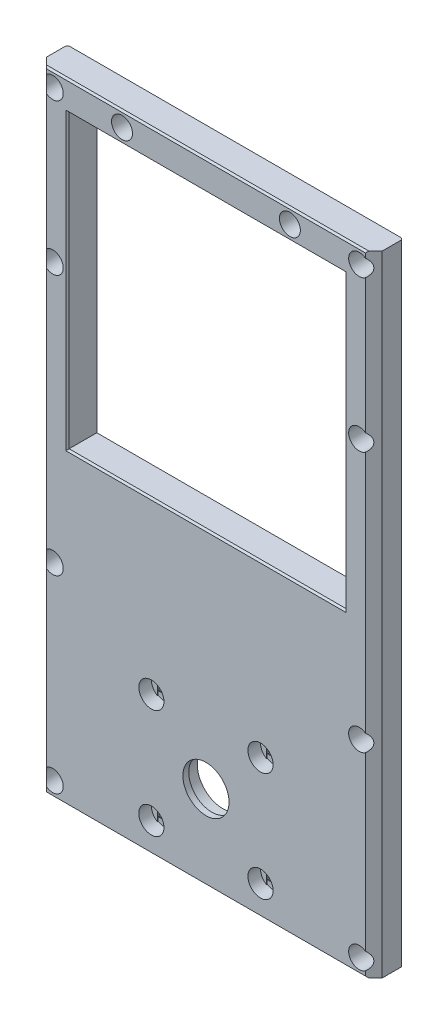
SolidWorks part; units mm, degrees
ref_plane "Front Plane" through (0, 0, 0) normal (0, 0, 1) x (1, 0, 0)
ref_plane "Top Plane" through (0, 0, 0) normal (0, 1, 0) x (1, 0, 0)
ref_plane "Right Plane" through (0, 0, 0) normal (1, 0, 0) x (0, 0, -1)
sketch "Sketch1" plane through (0, 0, 0) normal (0, 0, 1) x (1, 0, 0)
  line L1 (-40, -75) -> (40, -75)
  line L2 (-40, -75) -> (-40, 75)
  line L3 (-40, 75) -> (40, 75)
  line L4 (40, -75) -> (40, 75)
  line L5 (-40, -75) -> (40, 75) construction
  line L6 (-40, 75) -> (40, -75) construction
  line L7 (-33, -68) -> (33, -68)
  line L8 (-33, -68) -> (-33, 68)
  line L9 (-33, 68) -> (33, 68)
  line L10 (33, -68) -> (33, 68)
  line L11 (-33, -68) -> (33, 68) construction
  line L12 (-33, 68) -> (33, -68) construction
  point P0 (0, 0)
  point P6 (0, 0)
  dimension "D1" = 150
  dimension "D2" = 80
  dimension "D3" = 7
  dimension "D4" = 7
extrude "Boss-Extrude1" add sketch "Sketch1" along normal blind 7
sketch "Sketch2" plane through (0, 0, 7) normal (0, 0, 1) x (1, 0, 0)
  line L0 (33, -68) -> (33, 68) construction
  line L1 (-33, -68) -> (33, -68)
  line L2 (-33, -68) -> (-33, -32)
  line L3 (-33, -32) -> (33, -32)
  line L4 (33, -68) -> (33, -32)
  dimension "D1" = 36
extrude "Boss-Extrude2" add sketch "Sketch2" against normal up to surface (7 mm away) up to face at (0, 0, 0)
sketch "Sketch3" plane through (0, 0, 0) normal (0, 0, -1) x (-1, 0, 0)
  line L0 (0, -75) -> (0, -55) construction
  line L1 (40, -75) -> (-40, -75) construction
  circle A0 centre (0, -55) radius 5.5
  dimension "D1" = 11
  dimension "D2" = 20
extrude "Cut-Extrude1" cut sketch "Sketch3" against normal through all
sketch "Sketch4" plane through (0, 0, 0) normal (0, 0, -1) x (-1, 0, 0)
  circle A0 centre (0, -55) radius 6.05
  dimension "D1" = 12.1
extrude "Cut-Extrude2" cut sketch "Sketch4" against normal offset from surface (5.6 mm away) 1.4 up to face at (-5.5, -55, 7)
sketch "Sketch5" plane through (0, 0, 0) normal (0, 0, -1) x (-1, 0, 0)
  circle A0 centre (0, -55) radius 11.1
  dimension "D1" = 22.2
extrude "Cut-Extrude3" cut sketch "Sketch5" against normal offset from surface (3 mm away) 2.6 up to face at (-6.05, -55, 5.6)
sketch "Sketch6" plane through (0, 0, 0) normal (0, 0, -1) x (-1, 0, 0)
  line L1 (-13, -68) -> (13, -68) construction
  line L2 (-13, -68) -> (-13, -42) construction
  line L3 (-13, -42) -> (13, -42) construction
  line L4 (13, -68) -> (13, -42) construction
  line L5 (-13, -68) -> (13, -42) construction
  line L6 (-13, -42) -> (13, -68) construction
  circle A0 centre (-13, -42) radius 1.6
  circle A1 centre (13, -42) radius 1.6
  circle A2 centre (13, -68) radius 1.6
  circle A3 centre (-13, -68) radius 1.6
  point P0 (0, -55)
  dimension "D2" = 3.2
  dimension "D1" = 26
extrude "Cut-Extrude4" cut sketch "Sketch6" against normal through all
sketch "Sketch7" plane through (0, 0, 0) normal (0, 0, -1) x (-1, 0, 0)
  line L1 (-25, -74) -> (25, -74)
  line L2 (-25, -74) -> (-25, -36)
  line L3 (-25, -36) -> (25, -36)
  line L4 (25, -74) -> (25, -36)
  line L5 (-25, -74) -> (25, -36) construction
  line L6 (-25, -36) -> (25, -74) construction
  point P0 (0, -55)
  dimension "D1" = 50
  dimension "D2" = 38
extrude "Cut-Extrude5" cut sketch "Sketch7" against normal blind 1
sketch "Sketch8" plane through (0, 0, 7) normal (0, 0, 1) x (1, 0, 0)
  circle A0 centre (-13, -42) radius 3
  circle A1 centre (13, -42) radius 3
  circle A2 centre (13, -68) radius 3
  circle A3 centre (-13, -68) radius 3
  dimension "D1" = 6
extrude "Cut-Extrude6" cut sketch "Sketch8" against normal blind 3
sketch "Sketch9" plane through (0, 0, 7) normal (0, 0, 1) x (1, 0, 0)
  line L0 (-40, 75) -> (-40, -75) construction
  line L1 (-36.5, -71.5) -> (36.5, -71.5) construction
  line L2 (-36.5, -71.5) -> (-36.5, 71.5) construction
  line L3 (-36.5, 71.5) -> (36.5, 71.5) construction
  line L4 (36.5, -71.5) -> (36.5, 71.5) construction
  line L5 (-36.5, -71.5) -> (36.5, 71.5) construction
  line L6 (-36.5, 71.5) -> (36.5, -71.5) construction
  line L7 (40, 75) -> (-40, 75) construction
  circle A0 centre (-36.5, 71.5) radius 1.35
  circle A1 centre (36.5, 71.5) radius 1.35
  circle A2 centre (36.5, -71.5) radius 1.35
  circle A3 centre (-36.5, -71.5) radius 1.35
  circle A6 centre (-36.5, 35.5) radius 1.35
  circle A7 centre (-36.5, -26.5) radius 1.35
  circle A8 centre (36.5, -26.5) radius 1.35
  circle A9 centre (36.5, 35.5) radius 1.35
  point P0 (0, 0)
  dimension "D3" = 2.7
  dimension "D4" = 45
  dimension "D5" = 36
  dimension "D1" = 3.5
  dimension "D2" = 3.5
extrude "Cut-Extrude7" cut sketch "Sketch9" against normal through all
sketch "Sketch10" plane through (0, 0, 7) normal (0, 0, 1) x (1, 0, 0)
  circle A0 centre (-36.5, 71.5) radius 2.5
  circle A1 centre (36.5, 71.5) radius 2.5
  circle A2 centre (-36.5, 35.5) radius 2.5
  circle A3 centre (-36.5, -26.5) radius 2.5
  circle A4 centre (-36.5, -71.5) radius 2.5
  circle A5 centre (36.5, -71.5) radius 2.5
  circle A6 centre (36.5, 35.5) radius 2.5
  circle A7 centre (36.5, -26.5) radius 2.5
  dimension "D1" = 5
extrude "Cut-Extrude8" cut sketch "Sketch10" against normal blind 5
chamfer "Chamfer1" distance 2 angle 45 2 edges at (-40, 0, 7) (40, 0, 7)
sketch "Sketch11" plane through (0, 0, 7) normal (0, 0, 1) x (1, 0, 0)
  line L0 (33, -32) -> (33, 68) construction
  line L1 (-33, -32) -> (33, -32)
  line L2 (-33, -32) -> (-33, -1.5)
  line L3 (-33, -1.5) -> (33, -1.5)
  line L4 (33, -32) -> (33, -1.5)
  line L5 (-38, -75) -> (38, -75) construction
  dimension "D1" = 73.5
extrude "Boss-Extrude3" add sketch "Sketch11" against normal up to surface (7 mm away) up to face at (37.85, 71.5, 0)
sketch "Sketch12" plane through (0, 0, 2) normal (0, 0, 1) x (1, 0, 0)
  line L2 (-37.85, -73.6042) -> (-37.85, -69.3958)
  line L4 (-35.15, -73.6042) -> (-35.15, -69.3958)
  line L5 (-37.85, -73.6042) -> (-35.15, -69.3958) construction
  line L6 (-37.85, -69.3958) -> (-35.15, -73.6042) construction
  line L8 (-37.85, -28.6042) -> (-37.85, -24.3958)
  line L10 (-35.15, -28.6042) -> (-35.15, -24.3958)
  line L11 (-37.85, -28.6042) -> (-35.15, -24.3958) construction
  line L12 (-37.85, -24.3958) -> (-35.15, -28.6042) construction
  line L14 (-37.85, 33.3958) -> (-37.85, 37.6042)
  line L16 (-35.15, 33.3958) -> (-35.15, 37.6042)
  line L17 (-37.85, 33.3958) -> (-35.15, 37.6042) construction
  line L18 (-37.85, 37.6042) -> (-35.15, 33.3958) construction
  line L20 (-37.85, 69.3958) -> (-37.85, 73.6042)
  line L22 (-35.15, 69.3958) -> (-35.15, 73.6042)
  line L23 (-37.85, 69.3958) -> (-35.15, 73.6042) construction
  line L24 (-37.85, 73.6042) -> (-35.15, 69.3958) construction
  arc A0 (-38, -73.5) -> (-38, -69.5) centre (-36.5, -71.5) ccw construction
  circle A1 centre (-36.5, -26.5) radius 2.5 construction
  circle A2 centre (-36.5, 35.5) radius 2.5 construction
  arc A3 (-38, 69.5) -> (-38, 73.5) centre (-36.5, 71.5) ccw construction
  circle A4 centre (-36.5, 71.5) radius 1.35 construction
  circle A5 centre (-36.5, 71.5) radius 2.5 construction
  arc A6 (-35.15, 73.6042) -> (-37.85, 73.6042) centre (-36.5, 71.5) ccw
  arc A7 (-37.85, 69.3958) -> (-35.15, 69.3958) centre (-36.5, 71.5) ccw
  circle A8 centre (-36.5, 35.5) radius 1.35 construction
  arc A9 (-37.85, 33.3958) -> (-35.15, 33.3958) centre (-36.5, 35.5) ccw
  arc A10 (-35.15, 37.6042) -> (-37.85, 37.6042) centre (-36.5, 35.5) ccw
  circle A11 centre (-36.5, -26.5) radius 1.35 construction
  arc A12 (-37.85, -28.6042) -> (-35.15, -28.6042) centre (-36.5, -26.5) ccw
  arc A13 (-35.15, -24.3958) -> (-37.85, -24.3958) centre (-36.5, -26.5) ccw
  circle A14 centre (-36.5, -71.5) radius 1.35 construction
  arc A16 (-37.85, -73.6042) -> (-35.15, -73.6042) centre (-36.5, -71.5) ccw
  arc A18 (-35.15, -69.3958) -> (-37.85, -69.3958) centre (-36.5, -71.5) ccw
  point P0 (-36.5, -71.5)
  point P9 (-36.5, -26.5)
  point P17 (-36.5, 35.5)
  point P25 (-36.5, 71.5)
extrude "Cut-Extrude9" cut sketch "Sketch12" against normal blind 0.2
sketch "Sketch13" plane through (0, 0, 1.8) normal (0, 0, 1) x (1, 0, 0)
  line L0 (-35.15, -71.5) -> (-35.15, -69.3958) construction
  line L1 (-37.85, -72.85) -> (-35.15, -72.85)
  line L2 (-37.85, -72.85) -> (-37.85, -70.15)
  line L3 (-37.85, -70.15) -> (-35.15, -70.15)
  line L4 (-35.15, -72.85) -> (-35.15, -70.15)
  line L5 (-37.85, -72.85) -> (-35.15, -70.15) construction
  line L6 (-37.85, -70.15) -> (-35.15, -72.85) construction
  line L7 (-35.15, -26.5) -> (-35.15, -24.3958) construction
  line L8 (-37.85, -27.85) -> (-35.15, -27.85)
  line L9 (-37.85, -27.85) -> (-37.85, -25.15)
  line L10 (-37.85, -25.15) -> (-35.15, -25.15)
  line L11 (-35.15, -27.85) -> (-35.15, -25.15)
  line L12 (-37.85, -27.85) -> (-35.15, -25.15) construction
  line L13 (-37.85, -25.15) -> (-35.15, -27.85) construction
  line L14 (-35.15, 33.3958) -> (-35.15, 37.6042) construction
  line L15 (-37.85, 34.15) -> (-35.15, 34.15)
  line L16 (-37.85, 34.15) -> (-37.85, 36.85)
  line L17 (-37.85, 36.85) -> (-35.15, 36.85)
  line L18 (-35.15, 34.15) -> (-35.15, 36.85)
  line L19 (-37.85, 34.15) -> (-35.15, 36.85) construction
  line L20 (-37.85, 36.85) -> (-35.15, 34.15) construction
  line L21 (-35.15, 69.3958) -> (-35.15, 73.6042) construction
  line L22 (-37.85, 70.15) -> (-35.15, 70.15)
  line L23 (-37.85, 70.15) -> (-37.85, 72.85)
  line L24 (-37.85, 72.85) -> (-35.15, 72.85)
  line L25 (-35.15, 70.15) -> (-35.15, 72.85)
  line L26 (-37.85, 70.15) -> (-35.15, 72.85) construction
  line L27 (-37.85, 72.85) -> (-35.15, 70.15) construction
  arc A0 (-35.15, -71.5) -> (-37.85, -71.5) centre (-36.5, -71.5) ccw construction
  arc A1 (-35.15, -26.5) -> (-37.85, -26.5) centre (-36.5, -26.5) ccw construction
  arc A2 (-35.15, 35.5) -> (-37.85, 35.5) centre (-36.5, 35.5) ccw construction
  arc A3 (-35.15, 71.5) -> (-37.85, 71.5) centre (-36.5, 71.5) ccw construction
  point P0 (-36.5, -71.5)
  point P11 (-36.5, -26.5)
  point P22 (-36.5, 35.5)
  point P33 (-36.5, 71.5)
extrude "Cut-Extrude10" cut sketch "Sketch13" against normal blind 0.2
sketch "Sketch14" plane through (0, 0, 4) normal (0, 0, 1) x (1, 0, 0)
  line L2 (-14.6, -44.5377) -> (-14.6, -39.4623)
  line L4 (-11.4, -44.5377) -> (-11.4, -39.4623)
  line L5 (-14.6, -44.5377) -> (-11.4, -39.4623) construction
  line L6 (-14.6, -39.4623) -> (-11.4, -44.5377) construction
  line L8 (-14.6, -70.5377) -> (-14.6, -65.4623)
  line L10 (-11.4, -70.5377) -> (-11.4, -65.4623)
  line L11 (-14.6, -70.5377) -> (-11.4, -65.4623) construction
  line L12 (-14.6, -65.4623) -> (-11.4, -70.5377) construction
  circle A0 centre (-13, -42) radius 3 construction
  circle A1 centre (-13, -68) radius 3 construction
  circle A2 centre (-13, -42) radius 3 construction
  arc A3 (-14.6, -44.5377) -> (-11.4, -44.5377) centre (-13, -42) ccw
  arc A4 (-14.6, -70.5377) -> (-11.4, -70.5377) centre (-13, -68) ccw
  circle A5 centre (-13, -42) radius 1.6 construction
  circle A6 centre (-13, -68) radius 1.6 construction
  arc A7 (-11.4, -39.4623) -> (-14.6, -39.4623) centre (-13, -42) ccw
  arc A8 (-11.4, -65.4623) -> (-14.6, -65.4623) centre (-13, -68) ccw
  point P0 (-13, -42)
  point P8 (-13, -68)
extrude "Cut-Extrude11" cut sketch "Sketch14" against normal blind 0.2
sketch "Sketch15" plane through (0, 0, 3.8) normal (0, 0, 1) x (1, 0, 0)
  line L0 (-11.4, -42) -> (-11.4, -39.4623) construction
  line L1 (-14.6, -43.6) -> (-11.4, -43.6)
  line L2 (-14.6, -43.6) -> (-14.6, -40.4)
  line L3 (-14.6, -40.4) -> (-11.4, -40.4)
  line L4 (-11.4, -43.6) -> (-11.4, -40.4)
  line L5 (-14.6, -43.6) -> (-11.4, -40.4) construction
  line L6 (-14.6, -40.4) -> (-11.4, -43.6) construction
  line L7 (-11.4, -68) -> (-11.4, -65.4623) construction
  line L8 (-14.6, -69.6) -> (-11.4, -69.6)
  line L9 (-14.6, -69.6) -> (-14.6, -66.4)
  line L10 (-14.6, -66.4) -> (-11.4, -66.4)
  line L11 (-11.4, -69.6) -> (-11.4, -66.4)
  line L12 (-14.6, -69.6) -> (-11.4, -66.4) construction
  line L13 (-14.6, -66.4) -> (-11.4, -69.6) construction
  arc A0 (-11.4, -68) -> (-14.6, -68) centre (-13, -68) ccw construction
  arc A1 (-14.6, -42) -> (-11.4, -42) centre (-13, -42) ccw construction
  point P0 (-13, -42)
  point P8 (-13, -68)
extrude "Cut-Extrude12" cut sketch "Sketch15" against normal blind 0.2
mirror "Mirror1" about plane through (0, 0, 0) normal (1, 0, 0) of "Cut-Extrude10", "Cut-Extrude11", "Cut-Extrude12", "Cut-Extrude9"
chamfer "Chamfer2" distance 0.4 angle 45 4 edges at (33, 33.25, 7) (0, 68, 7) (0, -1.5, 7) (-33, 33.25, 7)
chamfer "Chamfer3" distance 0.4 angle 45 4 edges at (-40, 0, 0) (40, 0, 0) (0, -75, 7) (0, 75, 7)
sketch "Sketch16" plane through (0, 0, 0) normal (1, 0, 0) x (0, 0, -1)
  line L0 (0, -4) -> (0, -15.4)
  line L1 (0, 75) -> (0, -75) construction
  line L2 (0, -15.4) -> (3.2, -12.2)
  line L3 (3.2, -12.2) -> (3.2, -7.2)
  line L4 (3.2, -7.2) -> (0, -4)
  line L5 (0, -15.4) -> (0, -19.4) construction
  line L6 (0.6, -7.7) -> (2.6, -7.7)
  line L7 (0.6, -7.7) -> (0.6, -11.7)
  line L8 (0.6, -11.7) -> (2.6, -11.7)
  line L9 (2.6, -7.7) -> (2.6, -11.7)
  line L10 (-1.046, -17.4) -> (12.8392, -17.4) construction
  line L11 (2.6, -27.1) -> (2.6, -23.1)
  line L12 (0.6, -23.1) -> (2.6, -23.1)
  line L13 (0.6, -27.1) -> (0.6, -23.1)
  line L14 (0.6, -27.1) -> (2.6, -27.1)
  line L15 (3.2, -27.6) -> (0, -30.8)
  line L16 (3.2, -22.6) -> (3.2, -27.6)
  line L17 (0, -19.4) -> (3.2, -22.6)
  line L18 (0, -30.8) -> (0, -19.4)
  point P10 (2.6, -9.7)
  point P11 (3.2, -9.7)
  point P24 (0, -17.4)
  dimension "D1" = 5
  dimension "D2" = 2
  dimension "D3" = 0.6
  dimension "D4" = 0.6
  dimension "D5" = 45
  dimension "D6" = 4
  dimension "D7" = 4
  dimension "D8" = 4
extrude "Boss-Extrude4" add sketch "Sketch16" along normal mid plane 2
pattern_linear "LPattern1" count 2 spacing 20 along (1, 0, 0) count 2 spacing 20 along (-1, 0, 0) of "Boss-Extrude4"
sketch "Sketch17" plane through (0, 0, 0) normal (0, 0, -1) x (-1, 0, 0)
  line L0 (-20, 71.5) -> (20, 71.5) construction
  line L1 (-39.6, 75) -> (39.6, 75) construction
  circle A0 centre (-36.5, 71.5) radius 1.35 construction
  circle A1 centre (-36.5, 71.5) radius 1.35 construction
  circle A2 centre (-20, 71.5) radius 1.35
  circle A3 centre (20, 71.5) radius 1.35
  point P3 (0, 71.5)
  point P6 (0, 75)
  dimension "D1" = 40
extrude "Cut-Extrude13" cut sketch "Sketch17" against normal through all
sketch "Sketch18" plane through (0, 0, 7) normal (0, 0, 1) x (1, 0, 0)
  circle A0 centre (-20, 71.5) radius 2.5
  circle A1 centre (20, 71.5) radius 2.5
  arc A2 (-38, 69.5) -> (-38, 73.5) centre (-36.5, 71.5) ccw construction
extrude "Cut-Extrude14" cut sketch "Sketch18" against normal up to surface (5 mm away) up to face at (34.575, 71.5, 2)
sketch "Sketch19" plane through (0, 0, 2) normal (0, 0, 1) x (1, 0, 0)
  line L2 (-21.35, 69.3958) -> (-21.35, 73.6042)
  line L4 (-18.65, 69.3958) -> (-18.65, 73.6042)
  line L5 (-21.35, 69.3958) -> (-18.65, 73.6042) construction
  line L6 (-21.35, 73.6042) -> (-18.65, 69.3958) construction
  line L8 (18.65, 69.3958) -> (18.65, 73.6042)
  line L10 (21.35, 69.3958) -> (21.35, 73.6042)
  line L11 (18.65, 69.3958) -> (21.35, 73.6042) construction
  line L12 (18.65, 73.6042) -> (21.35, 69.3958) construction
  circle A0 centre (-20, 71.5) radius 2.5 construction
  circle A1 centre (20, 71.5) radius 2.5 construction
  circle A2 centre (20, 71.5) radius 1.35 construction
  circle A3 centre (-20, 71.5) radius 1.35 construction
  circle A4 centre (-20, 71.5) radius 2.5 construction
  arc A5 (18.65, 69.3958) -> (21.35, 69.3958) centre (20, 71.5) ccw
  arc A6 (-18.65, 73.6042) -> (-21.35, 73.6042) centre (-20, 71.5) ccw
  arc A7 (21.35, 73.6042) -> (18.65, 73.6042) centre (20, 71.5) ccw
  arc A8 (-21.35, 69.3958) -> (-18.65, 69.3958) centre (-20, 71.5) ccw
  point P0 (-20, 71.5)
  point P8 (20, 71.5)
extrude "Cut-Extrude15" cut sketch "Sketch19" against normal blind 0.2
sketch "Sketch20" plane through (0, 0, 1.8) normal (0, 0, 1) x (1, 0, 0)
  line L0 (-18.65, 69.3958) -> (-18.65, 73.6042) construction
  line L1 (-21.35, 70.15) -> (-18.65, 70.15)
  line L2 (-21.35, 70.15) -> (-21.35, 72.85)
  line L3 (-21.35, 72.85) -> (-18.65, 72.85)
  line L4 (-18.65, 70.15) -> (-18.65, 72.85)
  line L5 (-21.35, 70.15) -> (-18.65, 72.85) construction
  line L6 (-21.35, 72.85) -> (-18.65, 70.15) construction
  line L7 (21.35, 71.5) -> (21.35, 73.6042) construction
  line L8 (18.65, 70.15) -> (21.35, 70.15)
  line L9 (18.65, 70.15) -> (18.65, 72.85)
  line L10 (18.65, 72.85) -> (21.35, 72.85)
  line L11 (21.35, 70.15) -> (21.35, 72.85)
  line L12 (18.65, 70.15) -> (21.35, 72.85) construction
  line L13 (18.65, 72.85) -> (21.35, 70.15) construction
  arc A0 (18.65, 71.5) -> (21.35, 71.5) centre (20, 71.5) ccw construction
  point P0 (-20, 71.5)
  point P8 (20, 71.5)
extrude "Cut-Extrude16" cut sketch "Sketch20" against normal blind 0.2
sketch "Skizze4" plane through (0, 0, 0) normal (0, 0, -1) x (-1, 0, 0)
  line L1 (21, -4) -> (-21, -4)
  line L2 (21, -4) -> (21, -30.8)
  line L3 (21, -30.8) -> (-21, -30.8)
  line L4 (-21, -4) -> (-21, -30.8)
extrude "Schnitt-Linear austragen1" cut sketch "Skizze4" along normal up to surface (3.2 mm away) up to face at (-20, -9.7, -3.2)
